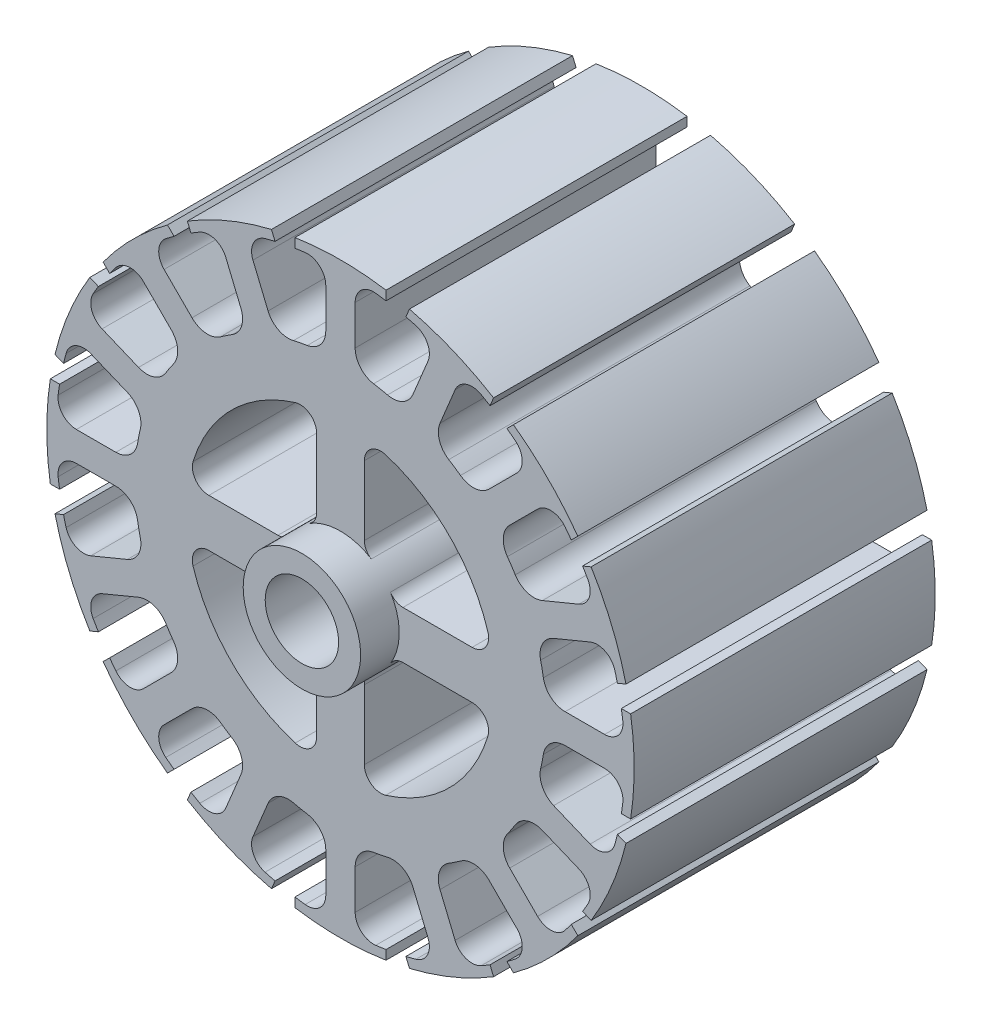
SolidWorks part; units mm, degrees
material "1023 Tôle d'acier au carbone (SS)"
ref_plane "Plan de face" through (0, 0, 0) normal (0, 0, 1) x (1, 0, 0)
ref_plane "Plan de dessus" through (0, 0, 0) normal (0, 1, 0) x (1, 0, 0)
ref_plane "Plan de droite" through (0, 0, 0) normal (1, 0, 0) x (0, 0, -1)
ref_axis "Axe1" through (0, 0, 0) along (0, 0, 1)
sketch "Esquisse1" plane through (0, 0, 0) normal (1, 0, 0) x (0, 0, -1)
  line L0 (0, 0) -> (-66.3235, 0) construction
  line L1 (-46.25, 40) -> (-46.25, 8)
  line L2 (-46.25, 40) -> (-5.25, 40)
  line L3 (-51.5, 8) -> (-51.5, 5)
  line L4 (-51.5, 5) -> (0, 5)
  line L5 (0, 8) -> (0, 5)
  line L6 (-46.25, 8) -> (-51.5, 8)
  line L7 (-5.25, 40) -> (-5.25, 8)
  line L8 (-5.25, 8) -> (0, 8)
  dimension "D1" = 10
  dimension "D2" = 80
  dimension "D3" = 51.5
  dimension "D4" = 41
  dimension "D5" = 16
revolve "Révolution1" add sketch "Esquisse1" angle 360 about L0
sketch "Esquisse3" plane through (0, 0, 0) normal (0, 0, 1) x (1, 0, 0)
  line L0 (0, 38.75) -> (0, 0) construction
  line L1 (-6.2, 39.5166) -> (-6.2, 38.2508)
  line L2 (-2, 35.9696) -> (-2, 30.5941)
  line L3 (0, 0) -> (-14.829, 35.8003) construction
  line L4 (0, 0) -> (-9.5305, 47.9132) construction
  line L5 (-11.9172, 33.9969) -> (-9.8601, 29.0306)
  line L6 (-9.3943, 38.8812) -> (-8.9099, 37.7118)
  arc A0 (-8.9099, 37.7118) -> (-10.2701, 37.3643) centre (0, 0) ccw
  arc A1 (-2, 35.9696) -> (-4.8103, 38.4503) centre (-4.5, 35.9696) ccw
  arc A2 (-4.5161, 27.6334) -> (-6.4025, 27.2582) centre (0, 0) ccw
  arc A3 (-11.9172, 33.9969) -> (-10.2701, 37.3643) centre (-9.6075, 34.9537) cw
  arc A4 (-9.3943, 38.8812) -> (-6.2, 39.5166) centre (0, 0) cw
  circle A5 centre (0, 0) radius 40 construction
  arc A6 (-4.8103, 38.4503) -> (-6.2, 38.2508) centre (0, 0) ccw
  arc A7 (-9.8601, 29.0306) -> (-6.4025, 27.2582) centre (-7.0885, 30.1787) ccw
  arc A8 (-4.5161, 27.6334) -> (-2, 30.5941) centre (-5, 30.5941) ccw
  point P19 (-8.84, 26.5679)
  point P26 (-2, 27.9285)
  dimension "D1" = 77.5
  dimension "D3" = 2.5
  dimension "D5" = 56
  dimension "D7" = 3
  dimension "D2" = 4
  dimension "D4" = 12.4
  dimension "D6" = 22.5
extrude "Enlèv. mat.-Extru.1" cut sketch "Esquisse3" along normal through all
pattern_circular "Répétition circulaire1" count 16 over 360 about axis through (0, 0, 0) along (0, 0, 1) of "Enlèv. mat.-Extru.1"
sketch "Esquisse4" plane through (0, 0, 0) normal (0, 0, 1) x (1, 0, 0)
  line L0 (0, 0) -> (0, 20.8518) construction
  line L1 (0, 0) -> (-16.8121, 16.8121) construction
  line L2 (-3.25, 17.9252) -> (-3.25, 8.511)
  line L3 (-17.9252, 3.25) -> (-8.511, 3.25)
  arc A0 (-3.25, 17.9252) -> (-6.16, 20.0762) centre (-5.5, 17.9252) ccw
  arc A1 (-6.16, 20.0762) -> (-20.0762, 6.16) centre (0, 0) ccw
  circle A2 centre (0, 0) radius 8 construction
  arc A3 (-4.2, 6.8088) -> (-6.8088, 4.2) centre (0, 0) ccw
  arc A4 (-17.9252, 3.25) -> (-20.0762, 6.16) centre (-17.9252, 5.5) cw
  arc A5 (-8.511, 3.25) -> (-6.8088, 4.2) centre (-8.511, 5.25) ccw
  arc A6 (-4.2, 6.8088) -> (-3.25, 8.511) centre (-5.25, 8.511) ccw
  point P15 (-7.3101, 3.25)
  point P18 (-3.25, 7.3101)
  dimension "D2" = 4.5
  dimension "D5" = 2
  dimension "D3" = 42
  dimension "D1" = 6.5
  dimension "D4" = 45
extrude "Enlèv. mat.-Extru.2" cut sketch "Esquisse4" along normal through all
pattern_circular "Répétition circulaire2" count 4 over 360 about axis through (0, 0, 0) along (0, 0, 1) of "Enlèv. mat.-Extru.2"
